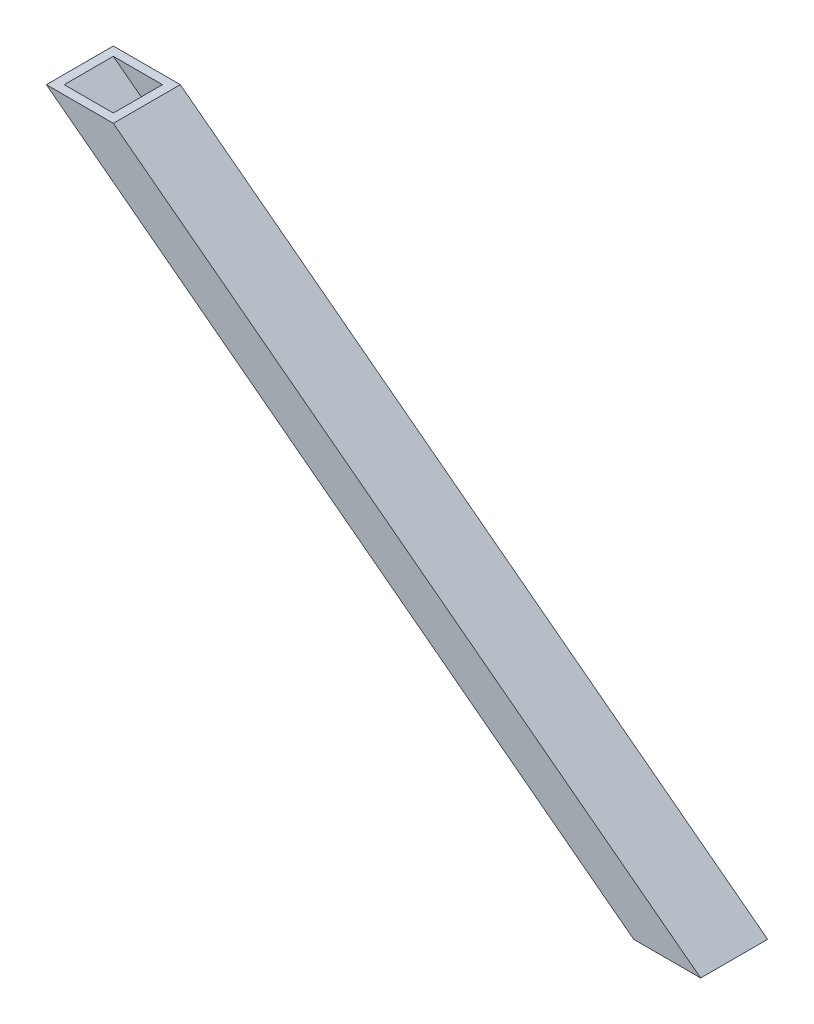
SolidWorks part; units mm, degrees
material "Ti-6Al-4VSolution treated and aged (SS)"
ref_plane "Front Plane" through (0, 0, 0) normal (0, 0, 1) x (1, 0, 0)
ref_plane "Top Plane" through (0, 0, 0) normal (0, 1, 0) x (1, 0, 0)
ref_plane "Right Plane" through (0, 0, 0) normal (1, 0, 0) x (0, 0, -1)
sketch "Sketch3" plane through (0, 0, 0) normal (0, 1, 0) x (1, 0, 0)
  line L25 (-37.5, 37.5) -> (37.5, 37.5)
  line L26 (-37.5, 37.5) -> (-37.5, -37.5)
  line L27 (-37.5, -37.5) -> (37.5, -37.5)
  line L28 (37.5, 37.5) -> (37.5, -37.5)
  line L29 (-37.5, 37.5) -> (37.5, -37.5) construction
  line L30 (-37.5, -37.5) -> (37.5, 37.5) construction
  line L31 (-27.5, 27.5) -> (27.5, 27.5)
  line L32 (-27.5, 27.5) -> (-27.5, -27.5)
  line L33 (-27.5, -27.5) -> (27.5, -27.5)
  line L34 (27.5, 27.5) -> (27.5, -27.5)
  line L35 (-27.5, 27.5) -> (27.5, -27.5) construction
  line L36 (-27.5, -27.5) -> (27.5, 27.5) construction
  point P0 (0, 0)
  point P5 (0, 0)
  dimension "D1" = 75
  dimension "D2" = 10
  dimension "D3" = 10
sketch "Sketch4" plane through (0, 0, 0) normal (0, 0, 1) x (1, 0, 0)
  line L0 (0, 0) -> (657.735, -500) construction
  dimension "D1" = 500
  dimension "D2" = 657.735
extrude "Boss-Extrude2" add sketch "Sketch3" along direction (0.7961, -0.6052, 0) on the side against the normal blind 826.205 contours L26 L25 L28 L27 | L32 L31 L34 L33
